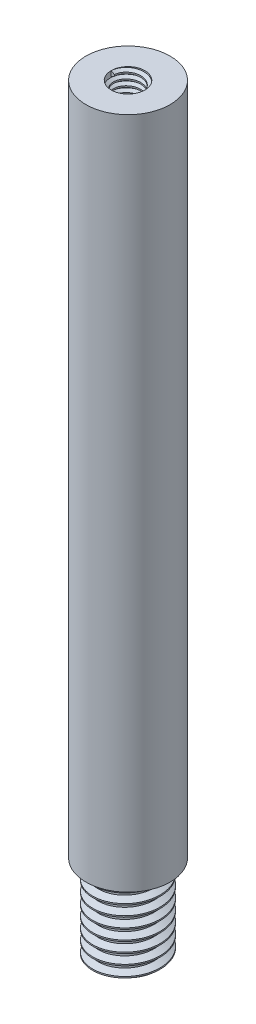
SolidWorks part; units mm, degrees
ref_plane "Front Plane" through (0, 0, 0) normal (0, 0, 1) x (1, 0, 0)
ref_plane "Top Plane" through (0, 0, 0) normal (0, 1, 0) x (1, 0, 0)
ref_plane "Right Plane" through (0, 0, 0) normal (1, 0, 0) x (0, 0, -1)
sketch "Sketch2" plane through (0, 0, 0) normal (0, 1, 0) x (1, 0, 0)
  circle A0 centre (0, 0) radius 5
  dimension "D1" = 10
extrude "Boss-Extrude1" add sketch "Sketch2" along normal blind 90
sketch "Sketch3" plane through (0, 0, 0) normal (0, -1, 0) x (1, 0, 0)
  circle A0 centre (0, 0) radius 4
  dimension "D1" = 8
extrude "Cut-Extrude2" cut sketch "Sketch3" against normal blind 10 flip side to cut
sketch "Sketch4" plane through (0, 90, 0) normal (0, 1, 0) x (1, 0, 0)
  circle A0 centre (0, 0) radius 2
  dimension "D1" = 4
extrude "Cut-Extrude3" cut sketch "Sketch4" against normal blind 10
thread "Thread2" pitch 1.25 method cut trim with end face yes profile "Thread Profile2" start angle 0, offset 0, length 0, pitch 1.25, diameter 8
ref_plane "Plane2" through (-4, 10, 0) normal (0, 0, 1) x (-1, 0, 0)
sketch "Thread Profile2" plane through (-4, 10, 0) normal (0, 0, 1) x (-1, 0, 0)
  line L0 (0, 0) -> (0, 1.25) construction
  line L11 (0, 0) -> (0, 1.0937)
  line L12 (0, 1.0937) -> (-0.6766, 0.7031)
  line L13 (-0.6766, 0.7031) -> (-0.6766, 0.3906)
  line L15 (-0.6766, 0.3906) -> (0, 0)
  line L17 (-0.6766, 0.5469) -> (0, 0.5469) construction
  point P2 (0, 0)
  dimension "Pitch" = 1.25
  dimension "Profile_Angle" = 60
  dimension "Profile_Land" = 0.3125
  dimension "Profile_Height" = 0.6766
thread "Thread4" pitch 0.7 method extrude trim with end face yes profile "Thread Profile4" start angle 0, offset 0, length 0, pitch 0.7, diameter 4
ref_plane "Plane4" through (-2, 90, 0) normal (0, 0, 1) x (-1, 0, 0)
sketch "Thread Profile4" plane through (-2, 90, 0) normal (0, 0, 1) x (-1, 0, 0)
  line L0 (0, 0) -> (0, 0.7) construction
  line L11 (0, 0) -> (0, 0.6125)
  line L12 (0, 0.6125) -> (-0.3789, 0.3937)
  line L13 (-0.3789, 0.3937) -> (-0.3789, 0.2187)
  line L15 (-0.3789, 0.2187) -> (0, 0)
  line L17 (-0.3789, 0.3062) -> (0, 0.3062) construction
  point P2 (0, 0)
  dimension "Pitch" = 0.7
  dimension "Profile_Angle" = 60
  dimension "Profile_Land" = 0.175
  dimension "Profile_Height" = 0.3789
sketch "Sketch7" plane through (0, 0, 0) normal (0, 0, -1) x (-1, 0, 0)
  line L4 (4, 10) -> (3.3234, 9.6094)
  line L6 (4, 10) -> (3.3234, 9.6094)
  line L7 (4, 8.9063) -> (4, 10)
  line L11 (4, 8.9063) -> (4, 10)
  line L13 (3.3234, 9.6094) -> (3.3234, 9.2969)
  line L15 (3.3234, 9.6094) -> (3.3234, 9.2969)
  line L16 (3.3234, 9.2969) -> (4, 8.9063)
  line L17 (3.3234, 9.2969) -> (4, 8.9063)
  dimension "D1" = 0
sketch "Sketch18" plane through (0, 0, 0) normal (0, 0, -1) x (-1, 0, 0)
  line L4 (4, 10) -> (3.3234, 9.6094)
  line L5 (3.3234, 9.6094) -> (3.3234, 9.2969)
  line L6 (3.3234, 9.2969) -> (4, 8.9063)
  line L7 (4, 8.9063) -> (4, 10)
  line L8 (4, 10) -> (3.3234, 9.6094)
  line L9 (3.3234, 9.6094) -> (3.3234, 9.2969)
  line L10 (3.3234, 9.2969) -> (4, 8.9063)
  line L11 (4, 8.9063) -> (4, 10)
  dimension "D1" = 0
extrude "Cut-Extrude9" cut sketch "Sketch18" against normal through all
